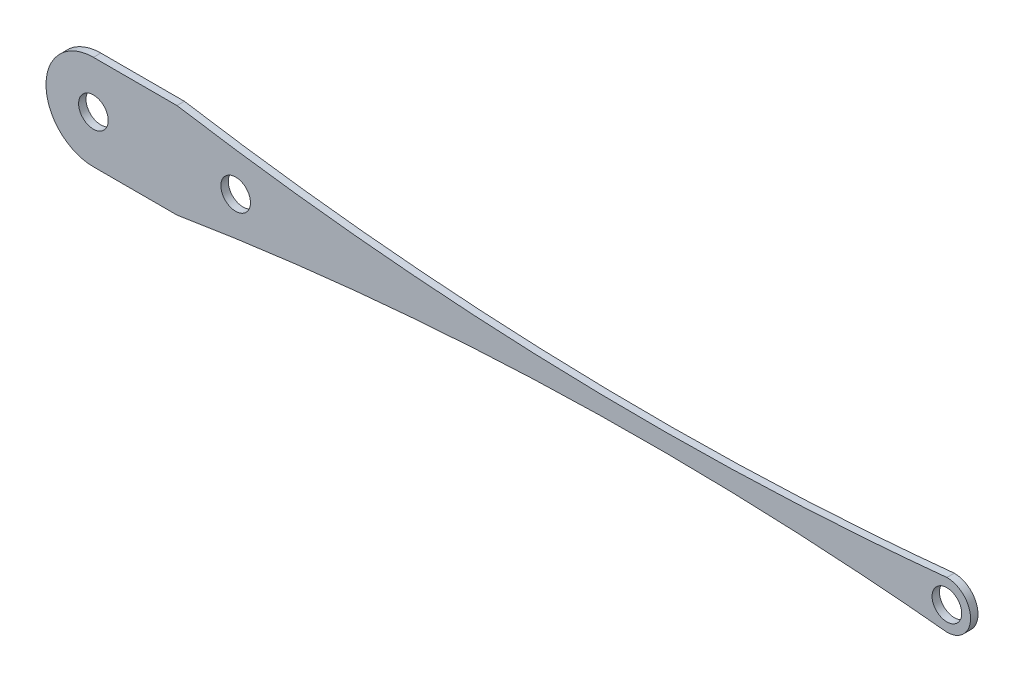
SolidWorks part; units mm, degrees
ref_plane "Front Plane" through (0, 0, 0) normal (0, 0, 1) x (1, 0, 0)
ref_plane "Top Plane" through (0, 0, 0) normal (0, 1, 0) x (1, 0, 0)
ref_plane "Right Plane" through (0, 0, 0) normal (1, 0, 0) x (0, 0, -1)
sketch "Sketch4" plane through (0, 0, 0) normal (0, 0, 1) x (1, 0, 0)
  line L0 (0, 0) -> (457.2, 0) construction
  line L1 (0, 25.4) -> (44.7423, 25.4)
  line L2 (0, -25.4) -> (44.7423, -25.4)
  arc A0 (0, 25.4) -> (0, -25.4) centre (0, 0) ccw
  circle A2 centre (0, 0) radius 7.9375
  circle A3 centre (76.2, 0) radius 7.9375
  circle A4 centre (457.2, 0) radius 7.9375
  arc A5 (457.2, -12.7) -> (457.2, 12.7) centre (457.2, 0) ccw
  arc A6 (44.7423, 25.4) -> (52.6769, 24.1289) centre (44.7423, 0) cw
  arc A7 (52.6769, -24.1289) -> (44.7423, -25.4) centre (44.7423, 0) cw
  spline S0 degree 2 poles (44.7423, 25.4) (249.9499, -8.0007) (457.2, 12.7) knots 0 0 0 1 1 1
  spline S1 degree 2 poles (44.7423, -25.4) (249.9499, 8.0007) (457.2, -12.7) knots 0 0 0 1 1 1
  point P3 (228.6, 0)
  dimension "D3" = 15.875
  dimension "D5" = 25.4
  dimension "D1" = 50.8
  dimension "D2" = 457.2
  dimension "D6" = 19.05
  dimension "D7" = 19.05
  dimension "D8" = 76.2
extrude "Boss-Extrude2" add sketch "Sketch4" along normal blind 3.9688 contours L2 S1 A5 S0 L1 A0 A2 A3 A4 region at (157.6607, 0, 0)
scale "Scale1" scale about centroid uniform scaling yes scale factor 0.75
